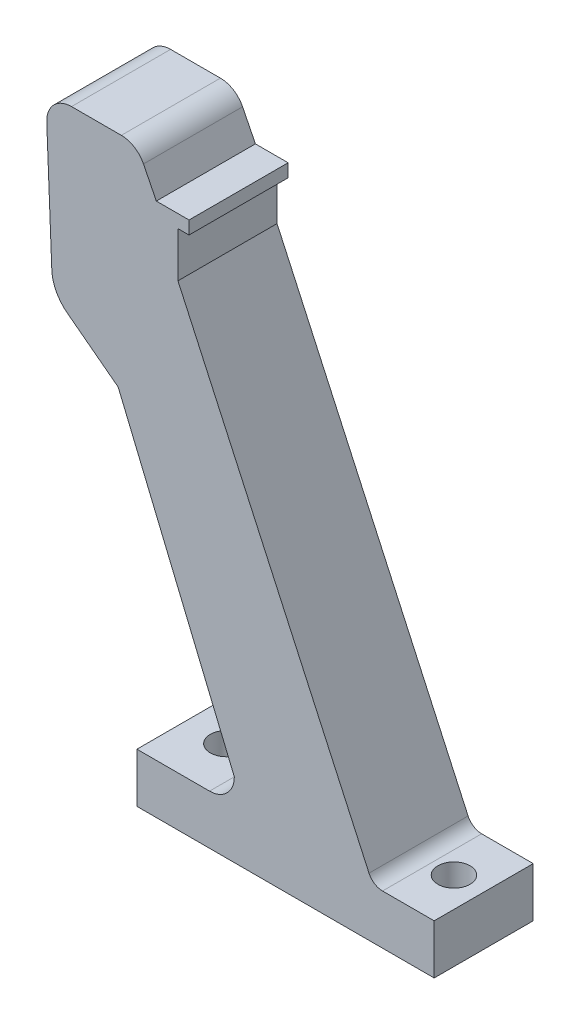
SolidWorks part; units mm, degrees
ref_plane "Front Plane" through (0, 0, 0) normal (0, 0, 1) x (1, 0, 0)
ref_plane "Top Plane" through (0, 0, 0) normal (0, 1, 0) x (1, 0, 0)
ref_plane "Right Plane" through (0, 0, 0) normal (1, 0, 0) x (0, 0, -1)
sketch "Sketch1" plane through (0, 0, 0) normal (0, 0, 1) x (1, 0, 0)
  line L2 (-44.0978, -34.8501) -> (-44.0978, -44.8501)
  line L3 (-44.0978, -44.8501) -> (15.9022, -44.8501)
  line L7 (-35.9155, -34.8501) -> (-44.0978, -34.8501)
  line L10 (-58.1484, 34.3679) -> (-47.8781, 26.5652)
  line L14 (-29.4383, -34.8501) -> (-35.9155, -34.8501)
  line L15 (15.9022, -44.8501) -> (15.9022, -34.8501)
  line L16 (15.9022, -34.8501) -> (5.4818, -34.8501)
  line L18 (-47.8781, 26.5652) -> (-24.4383, -29.8501)
  line L19 (15.8445, -44.8501) -> (15.9599, -44.8501) construction
  line L26 (-61.2932, 40.7066) -> (-62.2966, 65.6861)
  line L27 (-57.3007, 70.8868) -> (-47.2449, 70.8868)
  line L28 (-42.7704, 68.118) -> (-40.1809, 62.9247)
  line L29 (-35.8153, 51.168) -> (-35.8153, 60.292)
  line L30 (-33.5766, 60.292) -> (-33.5766, 62.9247)
  line L31 (-33.5766, 62.9247) -> (-40.1809, 62.9247)
  line L32 (-35.8153, 60.292) -> (-33.5766, 60.292)
  line L33 (-35.8153, 51.168) -> (2.754, -33.0986)
  arc A7 (-61.2932, 40.7066) -> (-58.1484, 34.3679) centre (-53.3327, 40.7066) ccw
  arc A14 (-24.4383, -29.8501) -> (-29.4383, -34.8501) centre (-29.4383, -29.8501) cw
  arc A17 (-62.2966, 65.6861) -> (-57.3007, 70.8868) centre (-57.3007, 65.8868) cw
  arc A18 (-47.2449, 70.8868) -> (-42.7704, 68.118) centre (-47.2449, 65.8868) cw
  arc A19 (5.4818, -34.8501) -> (2.754, -33.0986) centre (5.4818, -31.8501) cw
  dimension "D1" = 5
  dimension "D2" = 10
  dimension "D3" = 10
  dimension "D4" = 3
extrude "Boss-Extrude1" add sketch "Sketch1" along normal blind 20
sketch "Sketch3" plane through (0, -34.8501, 0) normal (0, 1, 0) x (1, 0, 0)
  line L0 (15.9022, -20) -> (15.9022, 0) construction
  circle A0 centre (9.9022, -10) radius 3.25
  circle A1 centre (-36.0384, -10) radius 3.25
  dimension "D2" = 6.5
  dimension "D3" = 6.5
  dimension "D1" = 6
extrude "Cut-Extrude1" cut sketch "Sketch3" against normal blind 20 and the other way blind 20
